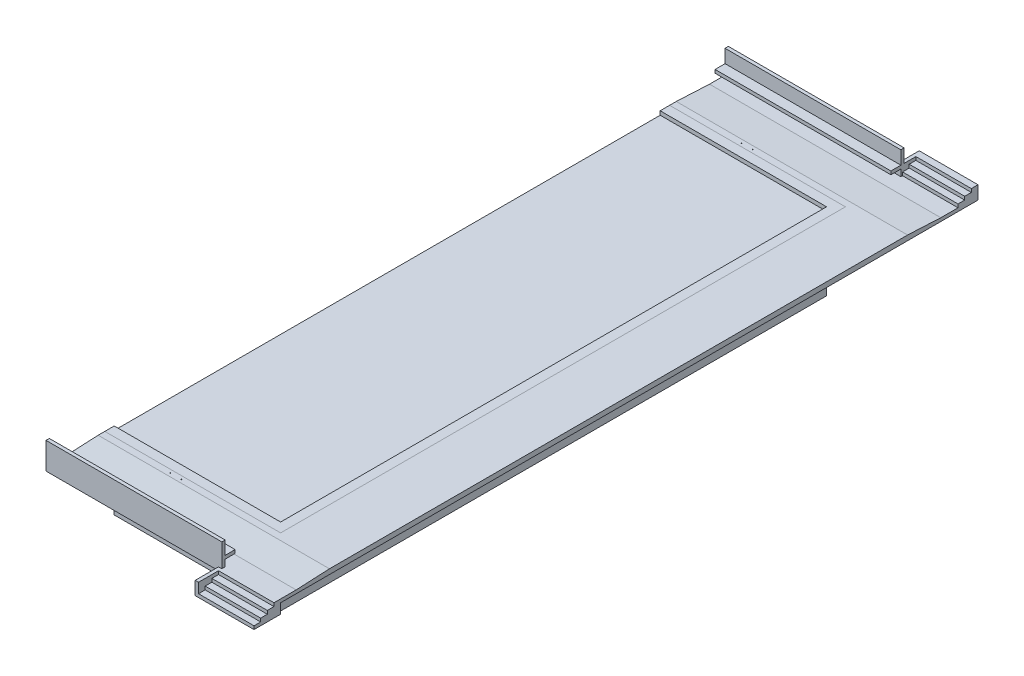
SolidWorks part; units mm, degrees
material "Water"
ref_plane "Front Plane" through (0, 0, 0) normal (0, 0, 1) x (1, 0, 0)
ref_plane "Top Plane" through (0, 0, 0) normal (0, 1, 0) x (1, 0, 0)
ref_plane "Right Plane" through (0, 0, 0) normal (1, 0, 0) x (0, 0, -1)
sketch "Sketch1" plane through (0, 0, 0) normal (0, 1, 0) x (1, 0, 0)
  line L1 (0, 0) -> (-7620, 0)
  line L2 (0, 0) -> (0, 25000.0008)
  line L3 (0, 25000.0008) -> (-7620, 25000.0008)
  line L4 (-7620, 0) -> (-7620, 25000.0008)
  dimension "D1" = 7620
  dimension "D2" = 25000.0008
extrude "Pool Water" add sketch "Sketch1" against normal blind 3352.8
sketch "Sketch2" plane through (0, 0, 0) normal (0, 1, 0) x (1, 0, 0)
  line L0 (-7620, 0) -> (-7620, -431.8)
  line L1 (-7620, -431.8) -> (431.8, -431.8)
  line L2 (431.8, -431.8) -> (431.8, 25431.8008)
  line L3 (431.8, 25431.8008) -> (-7620, 25431.8008)
  line L4 (-7620, 25431.8008) -> (-7620, 25000.0008)
  line L5 (0, 25000.0008) -> (-7620, 25000.0008) construction
  line L6 (0, 0) -> (0, 25000.0008) construction
  line L7 (-7620, 0) -> (0, 0)
  line L8 (0, 0) -> (0, 25000.0008)
  line L9 (0, 25000.0008) -> (-7620, 25000.0008)
  dimension "D1" = 431.8
  dimension "D2" = 431.8
  dimension "D3" = 431.8
extrude "Pool Deck Support" add sketch "Sketch2" along normal blind 101.6 and the other way blind 76.2 separate body
sketch "Sketch3" plane through (0, 101.6, 0) normal (0, 1, 0) x (1, 0, 0)
  line L0 (-7620, -2971.8) -> (-7620, -431.8)
  line L1 (-7620, -2971.8) -> (2971.8, -2971.8)
  line L3 (-7620, 27971.8008) -> (2971.8, 27971.8008)
  line L4 (2971.8, -2971.8) -> (2971.8, 27971.8008)
  line L5 (-7620, 25431.8008) -> (431.8, 25431.8008)
  line L6 (431.8, 25431.8008) -> (431.8, -431.8)
  line L7 (431.8, -431.8) -> (-7620, -431.8)
  line L8 (-7620, 25431.8008) -> (-7620, 27971.8008)
  dimension "D1" = 2540
  dimension "D2" = 2540
  dimension "D3" = 2540
extrude "Pool Deck" add sketch "Sketch3" against normal blind 152.4 separate body
sketch "Sketch4" plane through (0, -50.8, 0) normal (0, -1, 0) x (-1, 0, 0)
  line L0 (7620, -2971.8) -> (-2971.8, -2971.8) construction
  line L9 (-431.8, -3124.2) -> (7620, -3124.2)
  line L10 (-431.8, -3124.2) -> (-431.8, -2971.8)
  line L11 (-431.8, -2971.8) -> (7620, -2971.8)
  line L12 (7620, -3124.2) -> (7620, -2971.8)
  line L14 (7620, 27971.8008) -> (-431.8, 27971.8008)
  line L15 (7620, 27971.8008) -> (7620, 28124.2008)
  line L16 (7620, 28124.2008) -> (-431.8, 28124.2008)
  line L17 (-431.8, 27971.8008) -> (-431.8, 28124.2008)
  point P12 (7960.9392, -2971.8)
  point P13 (7742.386, -2971.8)
  point P15 (7530.7021, -2971.8)
  point P16 (7876.026, -2971.8)
  point P17 (7620, -2971.8)
  dimension "D1" = 152.4
  dimension "D2" = 152.4
  dimension "D3" = 8051.8
  dimension "D4" = 8051.8
extrude "Wall" add sketch "Sketch4" against normal blind 1219.2 separate body
sketch "Sketch7" plane through (0, 0, 2971.8) normal (0, 0, -1) x (-1, 0, 0)
  line L0 (-431.8, -50.8) -> (-431.8, 1168.4) construction
  line L1 (-431.8, 406.4) -> (7620, 406.4)
  line L2 (-431.8, 406.4) -> (-431.8, 558.8)
  line L3 (-431.8, 558.8) -> (7620, 558.8)
  line L4 (7620, 406.4) -> (7620, 558.8)
  line L5 (7620, -50.8) -> (7620, 1168.4) construction
  line L6 (7620, -50.8) -> (-2971.8, -50.8) construction
  dimension "D1" = 457.2
  dimension "D2" = 152.4
extrude "Near Side Bench" add sketch "Sketch7" along normal blind 457.2
sketch "Sketch8" plane through (0, 0, -27971.8008) normal (0, 0, 1) x (1, 0, 0)
  line L0 (-7620, -50.8) -> (-7620, 1168.4) construction
  line L1 (-7620, 558.8) -> (431.8, 558.8)
  line L2 (-7620, 558.8) -> (-7620, 406.4)
  line L3 (-7620, 406.4) -> (431.8, 406.4)
  line L6 (2971.8, -50.8) -> (-7620, -50.8) construction
  line L7 (431.8, 558.8) -> (431.8, 406.4)
  dimension "D1" = 152.4
  dimension "D2" = 457.2
  dimension "D3" = 8051.8
extrude "Far Side Bench" add sketch "Sketch8" along normal blind 457.2
sketch "Sketch9" plane through (2971.8, 0, 0) normal (1, 0, 0) x (0, 0, -1)
  line L0 (-3276.6, -50.8) -> (-3581.4, -50.8)
  line L1 (-2971.8, 101.6) -> (-3276.6, 101.6)
  line L2 (-2971.8, 101.6) -> (-2971.8, -291.9463)
  line L4 (-3276.6, 101.6) -> (-3276.6, -50.8)
  line L7 (-3581.4, -50.8) -> (-3581.4, -203.2)
  line L8 (-3581.4, -203.2) -> (-3886.2, -203.2)
  line L11 (-3886.2, -203.2) -> (-3886.2, -355.6)
  line L12 (-3886.2, -355.6) -> (-4191, -355.6)
  line L14 (-4160.2907, -508) -> (-4191, -508)
  line L15 (-4191, -355.6) -> (-4191, -508)
  line L16 (-4160.2907, -508) -> (-2971.8, -508)
  line L17 (-2971.8, -508) -> (-2971.8, -291.9463)
  line L18 (-2971.8, -50.8) -> (-2971.8, 101.6) construction
  line L19 (-2971.8, 101.6) -> (27971.8008, 101.6) construction
  dimension "D1" = 304.8
  dimension "D2" = 152.4
  dimension "D3" = 304.8
  dimension "D4" = 152.4
  dimension "D5" = 304.8
  dimension "D6" = 152.4
  dimension "D7" = 304.8
  dimension "D8" = 152.4
extrude "Stairs Down" add sketch "Sketch9" against normal up to surface (2540 mm away) up to face at (431.8, 520.7, 2895.6)
sketch "Sketch14" plane through (431.8, 0, 0) normal (1, 0, 0) x (0, 0, -1)
  line L0 (-431.8, 101.6) -> (-431.8, 177.8)
  line L1 (-431.8, 177.8) -> (-736.6, 177.8)
  line L6 (-736.6, 177.8) -> (-2260.6, 101.6)
  line L7 (-2260.6, 101.6) -> (-431.8, 101.6)
  dimension "D1" = 304.8
  dimension "D2" = 1828.8
extrude "Sloped Pool Deck Near Side" add sketch "Sketch14" against normal up to surface (8051.8 mm away) and the other way up to surface (2540 mm away) up to face at (-7620, 436.88, 2402.84) other way up to face at (2971.8, -177.8, -1677.4668)
sketch "Sketch15" plane through (0, 0, 431.8) normal (0, 0, -1) x (-1, 0, 0)
  line L0 (-431.8, 101.6) -> (-431.8, 177.8)
  line L1 (-431.8, 177.8) -> (-1346.2, 177.8)
  line L2 (-1346.2, 101.6) -> (-2260.6, 101.6)
  line L4 (-1346.2, 101.6) -> (-431.8, 101.6)
  line L5 (-2971.8, 101.6) -> (-2260.6, 101.6)
  line L6 (-2971.8, 101.6) -> (-2971.8, 177.8)
  line L7 (-2971.8, 177.8) -> (-1346.2, 177.8)
sketch "Sketch17" plane through (-7620, 0, 0) normal (-1, 0, 0) x (0, 0, 1)
  line L0 (-25431.8008, 101.6) -> (-25431.8008, 177.8)
  line L1 (-25431.8008, 177.8) -> (-25736.6008, 177.8)
  line L3 (-27260.6008, 101.6) -> (-25736.6008, 177.8)
  line L5 (-25431.8008, -50.8) -> (-25431.8008, 101.6) construction
  line L6 (-27971.8008, 101.6) -> (-25000.0008, 101.6) construction
  line L7 (-27260.6008, 101.6) -> (-25431.8008, 101.6)
  dimension "D1" = 1828.8
  dimension "D2" = 304.8
extrude "Sloped Pool Deck Far Side" add sketch "Sketch17" against normal up to surface (10591.8 mm away) up to face at (2971.8, -98.425, -1016.8001)
extrude "Sloped Pool Deck Length" add sketch "Sketch15" along normal up to surface (25863.6008 mm away) up to face at (-2324.1, 139.7, -25431.8008)
sketch "Sketch19" plane through (0, 101.6, 0) normal (0, 1, 0) x (1, 0, 0)
  line L0 (-7620, 0) -> (-7620, -431.8)
  line L1 (-7620, -431.8) -> (-7620, -736.6) construction
  line L2 (-7620, -431.8) -> (431.8, -431.8) construction
  line L3 (-7620, -431.8) -> (431.8, -431.8)
  line L4 (431.8, -431.8) -> (431.8, 25431.8008)
  line L5 (431.8, 25431.8008) -> (431.8, -431.8) construction
  line L6 (431.8, 25431.8008) -> (-7620, 25431.8008)
  line L7 (-7620, 25431.8008) -> (-7620, 25000.0008)
  line L8 (-7620, 25000.0008) -> (-7620, 0) construction
  line L9 (-7620, 25000.0008) -> (0, 25000.0008)
  line L10 (0, 25000.0008) -> (0, 0)
  line L11 (0, 0) -> (-7620, 0)
extrude "Drain Correction" cut sketch "Sketch19" against normal through all
sketch "Sketch20" plane through (0, 177.8, 0) normal (0, 1, 0) x (1, 0, 0)
  line L0 (-7620, 0) -> (-7620, -431.8)
  line L1 (-7620, -431.8) -> (431.8, -431.8)
  line L2 (431.8, -431.8) -> (431.8, 25431.8008)
  line L3 (431.8, 25431.8008) -> (-7620, 25431.8008)
  line L4 (431.8, 25431.8008) -> (-7620, 25431.8008) construction
  line L5 (-7620, 25431.8008) -> (-7620, 25000.0008)
  line L6 (-7620, 25000.0008) -> (-7620, 0) construction
  line L7 (-7620, 25000.0008) -> (0, 25000.0008)
  line L8 (0, 25000.0008) -> (0, 0)
  line L9 (0, 0) -> (-7620, 0)
sketch "Sketch21" plane through (2971.8, 0, 0) normal (1, 0, 0) x (0, 0, -1)
  line L0 (28657.6008, 406.4) -> (28352.8008, 406.4)
  line L1 (28962.4008, 558.8) -> (28657.6008, 558.8)
  line L3 (28657.6008, 558.8) -> (28657.6008, 406.4)
  line L4 (28352.8008, 406.4) -> (28352.8008, 254)
  line L5 (28352.8008, 254) -> (28048.0008, 254)
  line L6 (28048.0008, 254) -> (28048.0008, 101.6)
  line L7 (28048.0008, 101.6) -> (27743.2008, 101.6)
  line L9 (27743.2008, 101.6) -> (27743.2008, -50.8)
  line L12 (28962.4008, 558.8) -> (28962.4008, -50.8)
  line L13 (27743.2008, -50.8) -> (28962.4008, -50.8)
  dimension "D1" = 304.8
  dimension "D2" = 152.4
  dimension "D3" = 304.8
  dimension "D4" = 152.4
  dimension "D5" = 304.8
  dimension "D6" = 152.4
  dimension "D7" = 304.8
  dimension "D8" = 152.4
extrude "Stairs Up" add sketch "Sketch21" against normal up to surface (2540 mm away) up to face at (431.8, 520.7, -27895.6008)
extrude "Perimeter Drain" add sketch "Sketch20" against normal blind 228.6 separate body
sketch "Sketch23" plane through (0, 0, -25000.0008) normal (0, 0, 1) x (1, 0, 0)
  line L0 (0, -50.8) -> (0, 177.8) construction
  line L1 (-7620, 177.8) -> (0, 177.8) construction
  circle A0 centre (-5207, 25.4) radius 3.175
  circle A1 centre (-787.4, 25.4) radius 3.175
  dimension "D1" = 6.35
  dimension "D2" = 6.35
  dimension "D3" = 787.4
  dimension "D4" = 5207
  dimension "D5" = 152.4
  dimension "D6" = 152.4
extrude "Far Side Swim Lane Eyelets" cut sketch "Sketch23" against normal blind 152.4
sketch "Sketch25" plane through (0, 0, 0) normal (0, 0, -1) x (-1, 0, 0)
  line L0 (0, -50.8) -> (0, 177.8) construction
  line L1 (0, 177.8) -> (7620, 177.8) construction
  circle A0 centre (787.4, 25.4) radius 3.175
  circle A1 centre (5207, 25.4) radius 3.175
  dimension "D1" = 6.35
  dimension "D2" = 6.35
  dimension "D3" = 787.4
  dimension "D4" = 5207
  dimension "D5" = 152.4
  dimension "D6" = 152.4
extrude "Near Side Swim Lane Eyelets" cut sketch "Sketch25" against normal blind 152.4
sketch "Sketch26" plane through (431.8, 0, 0) normal (-1, 0, 0) x (0, 0, 1)
  line L1 (-28962.4008, 558.8) -> (-28124.2008, 558.8)
  line L2 (-28962.4008, 558.8) -> (-28962.4008, -50.8)
  line L3 (-28962.4008, -50.8) -> (-28124.2008, -50.8)
  line L4 (-28124.2008, 558.8) -> (-28124.2008, -50.8)
extrude "Far Side Stairs Wall" add sketch "Sketch26" along normal blind 152.4
sketch "Sketch27" plane through (431.8, 0, 0) normal (-1, 0, 0) x (0, 0, 1)
  line L1 (4191, -508) -> (3124.2, -508)
  line L2 (4191, -508) -> (4191, 101.6)
  line L3 (4191, 101.6) -> (3124.2, 101.6)
  line L4 (3124.2, -508) -> (3124.2, 101.6)
extrude "Near Side Stairs Wall" add sketch "Sketch27" along normal blind 152.4
sketch "Sketch28" plane through (0, 0, -27971.8008) normal (0, 0, 1) x (1, 0, 0)
  line L0 (431.8, 406.4) -> (431.8, 101.6) construction
  line L1 (-1397, 203.2) -> (-1295.4, 203.2)
  line L2 (-1397, 203.2) -> (-1397, 330.2)
  line L3 (-1397, 330.2) -> (-1295.4, 330.2)
  line L4 (-1295.4, 203.2) -> (-1295.4, 330.2)
  line L5 (431.8, 101.6) -> (-7620, 101.6) construction
  dimension "D1" = 127
  dimension "D2" = 101.6
  dimension "D3" = 1727.2
  dimension "D4" = 101.6
extrude "Far Side Electrical Box" add sketch "Sketch28" along normal blind 76.2 separate body
sketch "Sketch29" plane through (0, 0, -27895.6008) normal (0, 0, 1) x (1, 0, 0)
  line L0 (-1295.4, 330.2) -> (-1397, 330.2) construction
  line L1 (-1358.9, 304.8) -> (-1333.5, 304.8)
  line L2 (-1358.9, 304.8) -> (-1358.9, 279.4)
  line L3 (-1358.9, 228.6) -> (-1333.5, 228.6)
  line L4 (-1333.5, 304.8) -> (-1333.5, 279.4)
  line L5 (-1295.4, 203.2) -> (-1295.4, 330.2) construction
  line L6 (-1358.9, 254) -> (-1333.5, 254)
  line L7 (-1333.5, 279.4) -> (-1358.9, 279.4)
  line L8 (-1333.5, 254) -> (-1333.5, 228.6)
  line L9 (-1358.9, 254) -> (-1358.9, 228.6)
  dimension "D1" = 25.4
  dimension "D2" = 76.2
  dimension "D3" = 25.4
  dimension "D4" = 38.1
  dimension "D5" = 25.4
  dimension "D6" = 25.4
extrude "Far Side Outlets" add sketch "Sketch29" along normal blind 6.35 separate body
sketch "Sketch30" plane through (0, 0, 2971.8) normal (0, 0, -1) x (-1, 0, 0)
  line L0 (-431.8, 406.4) -> (-431.8, 101.6) construction
  line L1 (2108.2, 330.2) -> (2209.8, 330.2)
  line L2 (2108.2, 330.2) -> (2108.2, 203.2)
  line L3 (2108.2, 203.2) -> (2209.8, 203.2)
  line L4 (2209.8, 330.2) -> (2209.8, 203.2)
  line L5 (7620, 101.6) -> (-431.8, 101.6) construction
  dimension "D1" = 101.6
  dimension "D2" = 127
  dimension "D3" = 2540
  dimension "D4" = 101.6
extrude "Near Side Electrical Box" add sketch "Sketch30" along normal blind 76.2 separate body
sketch "Sketch31" plane through (0, 0, 2895.6) normal (0, 0, -1) x (-1, 0, 0)
  line L0 (2146.3, 304.8) -> (2171.7, 304.8)
  line L1 (2146.3, 304.8) -> (2146.3, 279.4)
  line L2 (2146.3, 228.6) -> (2171.7, 228.6)
  line L3 (2171.7, 304.8) -> (2171.7, 279.4)
  line L4 (2146.3, 254) -> (2171.7, 254)
  line L5 (2171.7, 279.4) -> (2146.3, 279.4)
  line L6 (2171.7, 254) -> (2171.7, 228.6)
  line L7 (2146.3, 254) -> (2146.3, 228.6)
  line L8 (2108.2, 330.2) -> (2108.2, 203.2) construction
  line L9 (2209.8, 330.2) -> (2108.2, 330.2) construction
  dimension "D1" = 25.4
  dimension "D2" = 76.2
  dimension "D3" = 25.4
  dimension "D4" = 25.4
  dimension "D5" = 38.1
  dimension "D6" = 25.4
extrude "Near Side Outlets" add sketch "Sketch31" along normal blind 6.35 separate body
sketch "Sketch32" plane through (0, 177.8, 0) normal (0, 1, 0) x (1, 0, 0)
  line L0 (0, 0) -> (-7620, 0) construction
  line L1 (0, 0) -> (0, 25000.0008) construction
  line L2 (0, 25000.0008) -> (0, 0) construction
  line L3 (-7620, 25000.0008) -> (0, 25000.0008) construction
  circle A0 centre (-4470.4, -584.2) radius 19.05
  circle A1 centre (-3962.4, -584.2) radius 19.05
  circle A2 centre (-4470.4, 25584.2008) radius 19.05
  circle A3 centre (-3962.4, 25584.2008) radius 19.05
  point P17 (0, 0)
  point P18 (0, 0)
  dimension "D1" = 508
  dimension "D4" = 38.1
  dimension "D5" = 38.1
  dimension "D7" = 38.1
  dimension "D8" = 38.1
  dimension "D2" = 584.2
  dimension "D3" = 3962.4
  dimension "D6" = 508
  dimension "D9" = 3962.4
  dimension "D10" = 584.2
extrude "Cut-Extrude4" cut sketch "Sketch32" against normal blind 152.4
